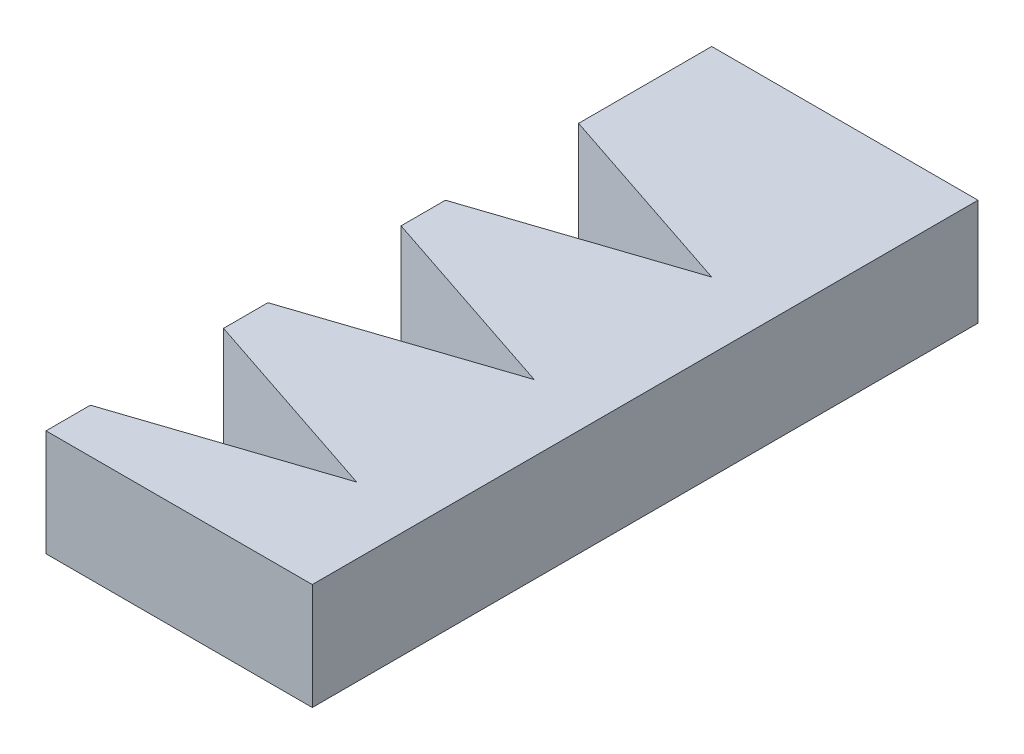
SolidWorks part; units mm, degrees
ref_plane "Front Plane" through (0, 0, 0) normal (0, 0, 1) x (1, 0, 0)
ref_plane "Top Plane" through (0, 0, 0) normal (0, 1, 0) x (1, 0, 0)
ref_plane "Right Plane" through (0, 0, 0) normal (1, 0, 0) x (0, 0, -1)
ref_axis "Axis1" through (0, 0, -147) along (0, 0, 1)
sketch "Sketch1" plane through (0, 0, 0) normal (0, 1, 0) x (1, 0, 0)
  line L1 (0, 0) -> (30, 0)
  line L2 (0, 0) -> (0, 75)
  line L3 (0, 75) -> (30, 75)
  line L4 (30, 0) -> (30, 75)
  dimension "D1" = 30
  dimension "D2" = 75
extrude "Boss-Extrude1" add sketch "Sketch1" along normal blind 12
sketch "Sketch3" plane through (0, 0, 0) normal (0, 1, 0) x (1, 0, 0)
  line L0 (0, 75) -> (0, 0) construction
  line L1 (0, 5) -> (22.5, 12.5)
  line L2 (22.5, 12.5) -> (0, 20)
  line L3 (30, 0) -> (30, 75) construction
  line L4 (0, 20) -> (0, 5) construction
  line L5 (0, 20) -> (0, 5)
  point P8 (0, 12.5)
  dimension "D1" = 5
  dimension "D2" = 7.5
  dimension "D3" = 15
extrude "Cut-Extrude1" cut sketch "Sketch3" along normal up to surface (12 mm away) up to face at (15, 12, -37.5)
pattern_linear "LPattern1" count 3 spacing 20 along (0, 0, -1) of "Cut-Extrude1"
